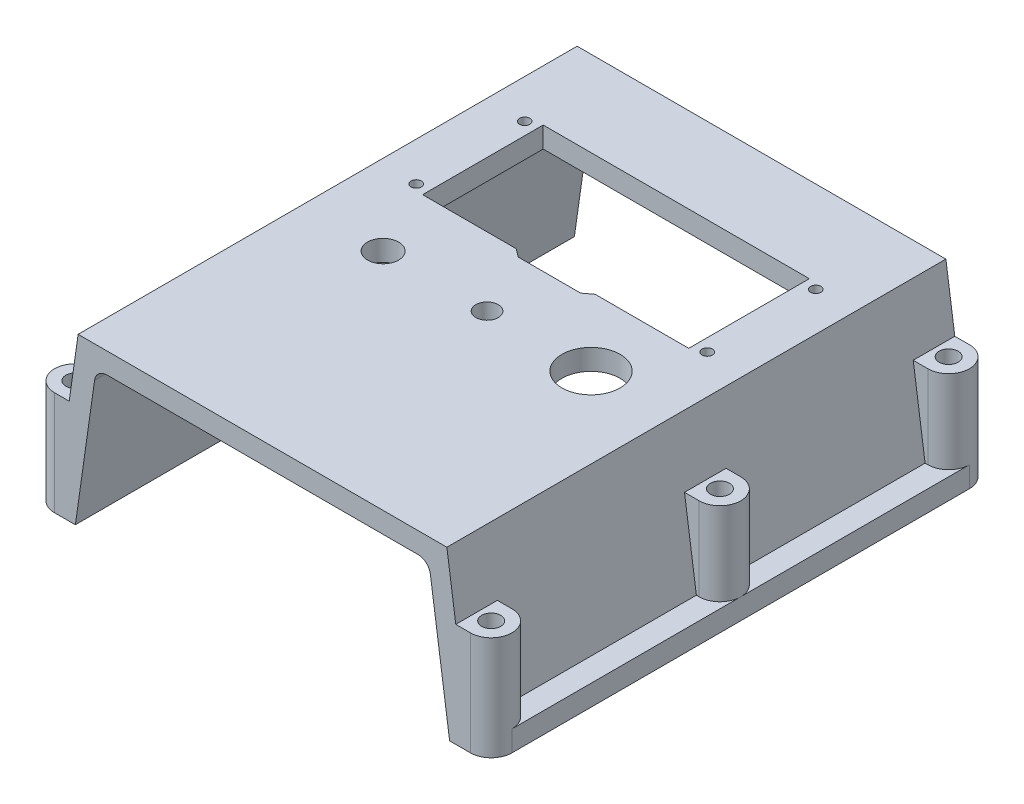
SolidWorks part; units mm, degrees
ref_plane "Front Plane" through (0, 0, 0) normal (0, 0, 1) x (1, 0, 0)
ref_plane "Top Plane" through (0, 0, 0) normal (0, 1, 0) x (1, 0, 0)
ref_plane "Right Plane" through (0, 0, 0) normal (1, 0, 0) x (0, 0, -1)
sketch "Sketch1" plane through (0, 0, 0) normal (0, 0, 1) x (1, 0, 0)
  line L1 (-45, -35) -> (-40, 0)
  line L2 (-40, 0) -> (40, 0)
  line L3 (-49.3365, -30) -> (-44.3365, 5)
  line L9 (-44.3365, 5) -> (44.3365, 5)
  line L10 (0, -55) -> (0, 55) construction
  line L11 (49.3365, -30) -> (44.3365, 5)
  line L12 (45, -35) -> (40, 0)
  line L15 (-55, -35) -> (-55, -30)
  line L16 (-55, -30) -> (-49.3365, -30)
  line L18 (55, -35) -> (55, -30)
  line L19 (55, -30) -> (49.3365, -30)
  line L20 (-55, -35) -> (-45, -35)
  line L21 (45, -35) -> (55, -35)
  point P7 (0, 5)
  point P13 (0, 5)
  point P15 (0, 0)
  dimension "D2" = 55
  dimension "D3" = 35
  dimension "D4" = 5
  dimension "D5" = 5
  dimension "D6" = 80
  dimension "D7" = 5
  dimension "D8" = 10
  dimension "D9" = 10
  dimension "D10" = 5
extrude "Boss-Extrude1" add sketch "Sketch1" along normal blind 120
fillet "Fillet1" radius 5 4 edges at (-55, -32.5, 120) (-55, -32.5, 0) (55, -32.5, 0) (55, -32.5, 120)
sketch "Sketch2" plane through (0, 5, 0) normal (0, 1, 0) x (1, 0, 0)
  line L0 (-32, -20.5) -> (-32, -49.5)
  line L5 (-9.5, -49.5) -> (-7.5, -51)
  line L6 (0, 0) -> (0, -120) construction
  line L7 (44.3365, -120) -> (-44.3365, -120) construction
  line L8 (-35, -21.95) -> (-35, -48.05) construction
  line L9 (38, -51) -> (-38, -51)
  line L10 (38, -51) -> (38, -19)
  line L11 (38, -19) -> (-38, -19)
  line L12 (-38, -51) -> (-38, -19)
  line L13 (38, -51) -> (-38, -19) construction
  line L14 (38, -19) -> (-38, -51) construction
  line L15 (-32, -20.5) -> (32, -20.5)
  line L16 (-32, -49.5) -> (-9.5, -49.5)
  line L17 (9.5, -49.5) -> (7.5, -51)
  line L18 (32, -49.5) -> (9.5, -49.5)
  line L19 (32, -20.5) -> (32, -49.5)
  line L20 (44.3365, 0) -> (-44.3365, 0) construction
  circle A0 centre (-35, -21.95) radius 1.25
  circle A1 centre (-35, -48.05) radius 1.25
  circle A2 centre (35, -48.05) radius 1.25
  circle A3 centre (35, -21.95) radius 1.25
  circle A4 centre (0, -66) radius 2.7
  circle A5 centre (-25, -66) radius 3.75
  circle A6 centre (25, -66) radius 7
  point P7 (0, -35)
  point P16 (-35, -35)
  point P28 (0, -20.5)
  dimension "D1" = 35
  dimension "D3" = 2.5
  dimension "D12" = 7.5
  dimension "D14" = 14
  dimension "D15" = 5.4
  dimension "D2" = 26.1
  dimension "D4" = 32
  dimension "D5" = 76
  dimension "D6" = 32
  dimension "D7" = 1.5
  dimension "D8" = 1.5
  dimension "D9" = 7.5
  dimension "D10" = 2
  dimension "D11" = 35
  dimension "D13" = 25
  dimension "15" = 15
  dimension "D16" = 25
extrude "Cut-Extrude1" cut sketch "Sketch2" against normal up to next contours L19 L15 L0 L16 L5 L9 L17 L18 | A0 | A1 | A3 | A6 | A4 | A5 | A2 region at (0, 5, 35.2063) region at (-35, 5, 21.95) region at (-35, 5, 48.05) region at (35, 5, 21.95) region at (0, 5, 66) region at (-25, 5, 66) region at (25, 5, 66)
sketch "Sketch3" plane through (0, -30, 0) normal (0, 1, 0) x (1, 0, 0)
  line L0 (-49.3365, -120) -> (-49.3365, 0) construction
  line L1 (-50, 0) -> (-45, 0)
  line L2 (-45, 0) -> (-45, -10)
  line L3 (-45, -10) -> (-50, -10)
  line L4 (-50, -55) -> (-45, -55)
  line L5 (-45, -55) -> (-45, -65)
  line L6 (-45, -65) -> (-50, -65)
  line L7 (-50, -110) -> (-45, -110)
  line L8 (-45, -110) -> (-45, -120)
  line L9 (-45, -120) -> (-50, -120)
  line L10 (50, -110) -> (45, -110)
  line L11 (45, -110) -> (45, -120)
  line L12 (45, -120) -> (50, -120)
  line L13 (50, -65) -> (45, -65)
  line L14 (45, -65) -> (45, -55)
  line L15 (45, -55) -> (50, -55)
  line L16 (50, 0) -> (45, 0)
  line L17 (45, 0) -> (45, -10)
  line L18 (45, -10) -> (50, -10)
  line L19 (-55, -115) -> (-55, -5) construction
  arc A0 (-50, 0) -> (-50, -10) centre (-50, -5) ccw
  arc A1 (50, -10) -> (50, 0) centre (50, -5) ccw
  arc A2 (50, -120) -> (50, -110) centre (50, -115) ccw
  arc A3 (-50, -110) -> (-50, -120) centre (-50, -115) ccw
  circle A4 centre (-50, -5) radius 2.3
  circle A5 centre (50, -5) radius 2.3
  circle A6 centre (50, -115) radius 2.3
  circle A7 centre (-50, -115) radius 2.3
  arc A8 (-50, -55) -> (-50, -65) centre (-50, -60) ccw
  circle A9 centre (-50, -60) radius 2.3
  arc A10 (50, -65) -> (50, -55) centre (50, -60) ccw
  circle A11 centre (50, -60) radius 2.3
  point P21 (-49.3365, -60)
  line M4 (-49.3365, -120) -> (-49.3365, 0)
  dimension "D1" = 4.6
extrude "Boss-Extrude2" add sketch "Sketch3" along normal blind 20
extrude "Cut-Extrude2" cut sketch "Sketch3<4>" against normal up to next and the other way blind 13 contours A4 M4 | A9 M4 | A9 M4 | A4 M4 | A7 M4 | A7 M4 | A6 | A11 | A5 region at (-50.629, -30, 5) region at (-48.6566, -30, 5) region at (-50.629, -30, 60) region at (-48.6566, -30, 60) region at (-50.629, -30, 115) region at (-48.6566, -30, 115) region at (50, -30, 115) region at (50, -30, 60)
sketch "Sketch3<4>" plane through (0, -30, 0) normal (0, 1, 0) x (1, 0, 0) same geometry as "Sketch3"
fillet "Fillet2" radius 3 2 edges at (40, 0, 60) (-40, 0, 60)
